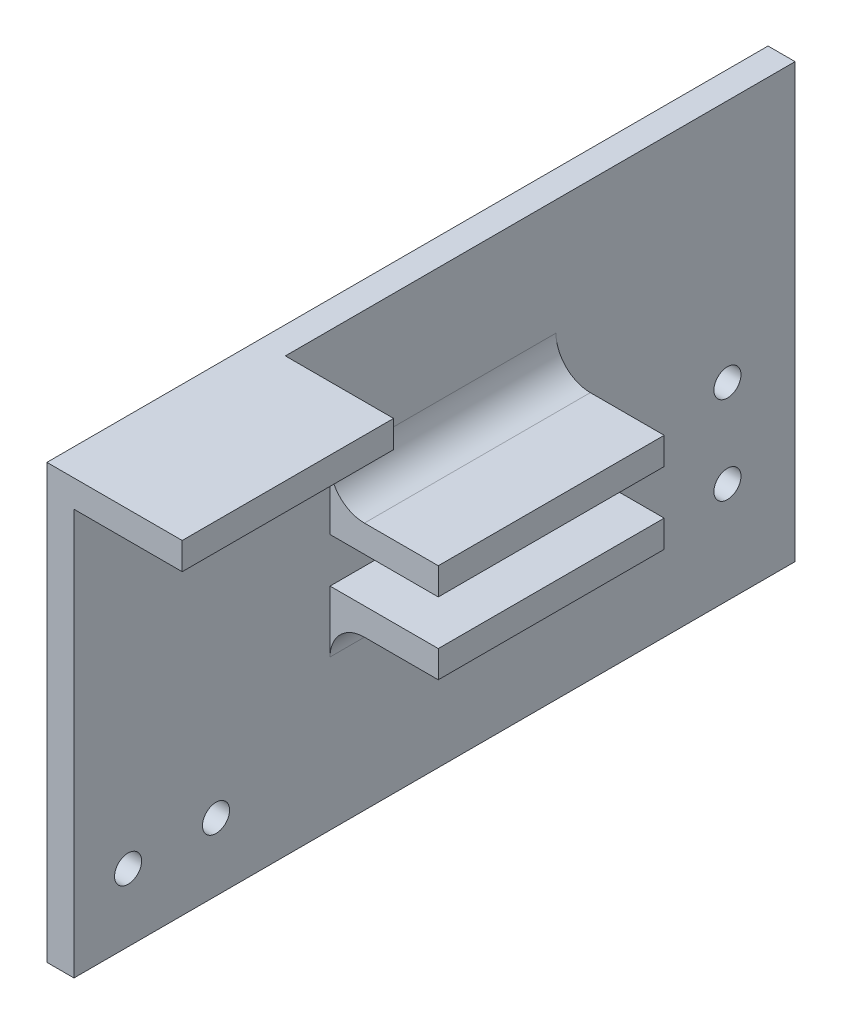
SolidWorks part; units mm, degrees
ref_plane "Front Plane" through (0, 0, 0) normal (0, 0, 1) x (1, 0, 0)
ref_plane "Top Plane" through (0, 0, 0) normal (0, 1, 0) x (1, 0, 0)
ref_plane "Right Plane" through (0, 0, 0) normal (1, 0, 0) x (0, 0, -1)
sketch "Sketch1" plane through (0, 0, 0) normal (1, 0, 0) x (0, 0, -1)
  line L0 (0, 14.732) -> (0, -17.275)
  line L1 (0, -17.275) -> (53.3, -17.275)
  line L2 (53.3, -17.275) -> (53.3, 14.732)
  line L3 (53.3, 14.732) -> (0, 14.732)
  line L4 (4, -12.275) -> (10.5, -12.275) construction
  line L5 (18.927, 3.651) -> (35.625, 3.651)
  line L6 (18.927, 3.651) -> (18.927, 1.651)
  line L7 (18.927, 1.651) -> (35.625, 1.651)
  line L8 (35.625, 3.651) -> (35.625, 1.651)
  line L9 (18.927, -1.651) -> (35.625, -1.651)
  line L10 (18.927, -1.651) -> (18.927, -3.651)
  line L11 (18.927, -3.651) -> (35.625, -3.651)
  line L12 (35.625, -1.651) -> (35.625, -3.651)
  line L13 (15.625, 14.732) -> (15.625, 3.675) construction
  line L14 (15.625, 3.675) -> (18.8, 3.675) construction
  line L15 (18.8, 3.675) -> (18.8, -8.875) construction
  line L16 (18.8, -8.875) -> (15.625, -8.875) construction
  line L17 (15.625, -8.875) -> (15.625, -17.275) construction
  line L18 (38.8, 1.651) -> (38.8, -1.651) construction
  line L19 (48.3, -9.8) -> (48.3, -3.3) construction
  line L24 (37.8, 0) -> (38.8, 0) construction
  line L26 (0, 14.732) -> (15.625, 14.732)
  line L27 (0, 14.732) -> (0, 12.732)
  line L28 (0, 12.732) -> (15.625, 12.732)
  line L29 (15.625, 14.732) -> (15.625, 12.732)
  circle A0 centre (4, -12.275) radius 1
  circle A1 centre (10.5, -12.275) radius 1
  circle A2 centre (48.3, -9.8) radius 1
  circle A3 centre (48.3, -3.3) radius 1
  point P19 (38.8, 0)
  point P24 (17.2125, 3.675)
  point P31 (37.8, 0)
  dimension "D1" = 2
  dimension "D9" = 3.4
  dimension "D2" = 6.5
  dimension "D3" = 3.302
  dimension "D4" = 2
  dimension "D5" = 5.125
  dimension "D6" = 4
  dimension "D7" = 5
  dimension "D8" = 3.175
  dimension "D10" = 12.55
  dimension "D11" = 3.675
  dimension "D12" = 0.127
  dimension "D13" = 2
  dimension "D14" = 9.057
  dimension "D15" = 20
  dimension "D16" = 6.35
  dimension "D17" = 10.5
  dimension "D18" = 3.3
  dimension "D19" = 1
  dimension "D20" = 5
extrude "Boss-Extrude1" add sketch "Sketch1" along normal blind 2 contours L28 L0 L1 L2 A3 A2 A1 A0 L5 L8 L7 L6 L9 L12 L11 L10 | L8 L5 L6 L7 | L12 L9 L10 L11 | L0 L28 L2 L3 region at (0, 13.732, -7.8125) region at (0, -1.5545, -26.9839) region at (0, 2.651, -27.276) region at (0, -2.651, -27.276)
extrude "Boss-Extrude2" add sketch "Sketch1<3>" along normal blind 10 contours L0 L28 L2 L3 | L8 L5 L6 L7 | L12 L9 L10 L11 region at (0, 13.732, -7.8125) region at (0, 2.651, -27.276) region at (0, -2.651, -27.276)
sketch "Sketch1<3>" plane through (0, 0, 0) normal (1, 0, 0) x (0, 0, -1) same geometry as "Sketch1"
fillet "Fillet1" radius 2.54 2 edges at (2, 3.651, -27.276) (2, -3.651, -27.276)
